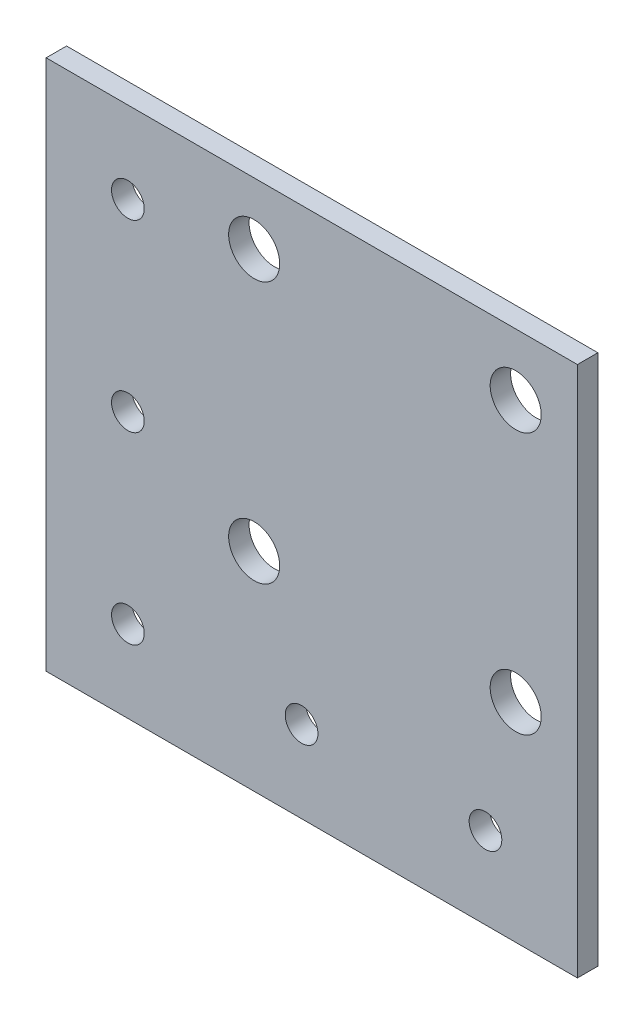
SolidWorks part; units mm, degrees
ref_plane "前视基准面" through (0, 0, 0) normal (0, 0, 1) x (1, 0, 0)
ref_plane "上视基准面" through (0, 0, 0) normal (0, 1, 0) x (1, 0, 0)
ref_plane "右视基准面" through (0, 0, 0) normal (1, 0, 0) x (0, 0, -1)
sketch "草图1" plane through (0, 0, 0) normal (0, 0, 1) x (1, 0, 0)
  line L0 (-82.9, -17.9) -> (-42.9, -17.9) construction
  line L3 (-42.9, -32.9) -> (-42.9, 32.9) construction
  line L4 (-82.9, 1957.1) -> (-82.9, -82.9) construction
  line L5 (-82.9, 47.1) -> (-82.9, -82.9)
  line L6 (-62.9, 47.1) -> (-62.9, -82.9) construction
  line L7 (-82.9, -82.9) -> (47.1, -82.9)
  line L8 (-82.9, -82.9) -> (-82.9, 47.1)
  line L9 (-82.9, 47.1) -> (47.1, 47.1)
  line L10 (47.1, -82.9) -> (47.1, 47.1)
  line L11 (-42.9, -62.9) -> (47.1, -62.9) construction
  line L12 (-42.9, -50.9) -> (-42.9, -74.9) construction
  line L13 (2.1, -62.9) -> (2.1, -50.9) construction
  line L14 (637.1, -50.9) -> (-42.9, -50.9) construction
  circle A0 centre (-32, -32) radius 6.25 construction
  circle A1 centre (-32, -32) radius 6.25
  circle A2 centre (-32, 32) radius 6.25 construction
  circle A3 centre (-32, 32) radius 6.25
  circle A4 centre (32, 32) radius 6.25 construction
  circle A5 centre (32, 32) radius 6.25
  circle A6 centre (32, -32) radius 6.25 construction
  circle A7 centre (32, -32) radius 6.25
  circle A8 centre (-62.9, 27.1) radius 4
  circle A9 centre (-62.9, -17.9) radius 4
  circle A10 centre (-62.9, -62.9) radius 4
  circle A11 centre (-20.4, -62.9) radius 4
  circle A12 centre (24.6, -62.9) radius 4
  point P41 (0, 0)
  dimension "D5" = 8
  dimension "D6" = 8
  dimension "D1" = 130
  dimension "D2" = 130
  dimension "D3" = 20
  dimension "D4" = 45
extrude "凸台-拉伸1" add sketch "草图1" along normal blind 5 contours L7 L10 L9 L5 A12 A11 A1 A3 A5 A7 A8 A9 A10 region at (-18.1483, -18.1638, 0)
